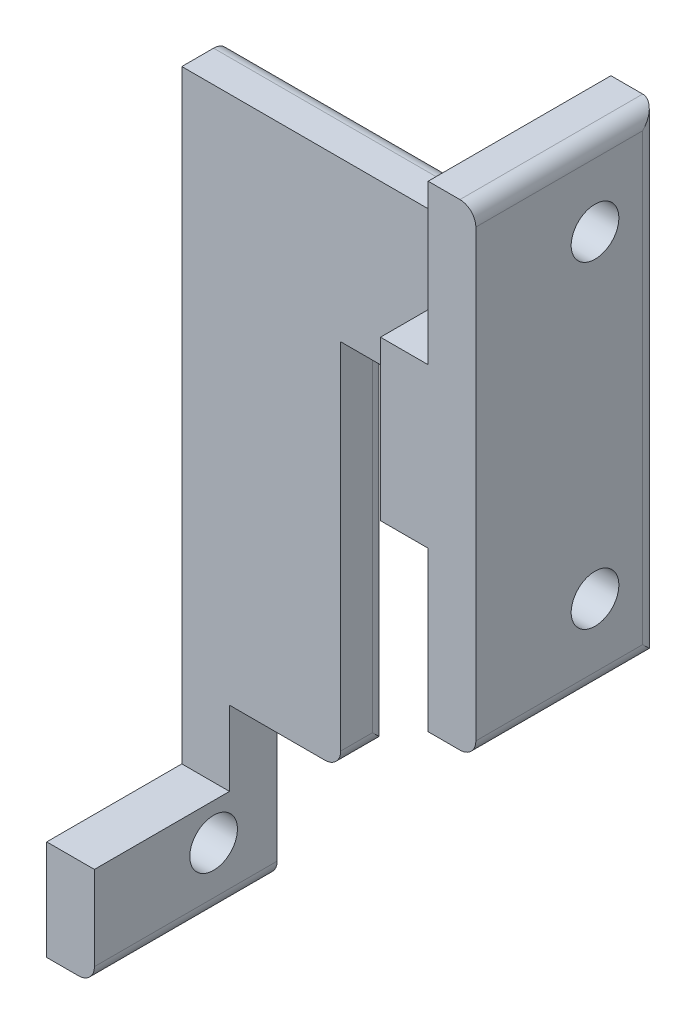
SolidWorks part; units mm, degrees
ref_plane "Alzado" through (0, 0, 0) normal (0, 0, 1) x (1, 0, 0)
ref_plane "Planta" through (0, 0, 0) normal (0, 1, 0) x (1, 0, 0)
ref_plane "Vista lateral" through (0, 0, 0) normal (1, 0, 0) x (0, 0, -1)
sketch "Croquis1" plane through (0, 0, 0) normal (1, 0, 0) x (0, 0, -1)
  line L1 (-23, 0) -> (0, 0)
  line L2 (-23, 0) -> (-23, -33.3)
  line L3 (-23, -33.3) -> (0, -33.3)
  line L4 (0, 0) -> (0, -33.3)
  dimension "D1" = 33.3
  dimension "D2" = 23
extrude "Saliente-Extruir2" add sketch "Croquis1" along normal blind 7
sketch "Croquis3" plane through (0, 0, 0) normal (0, 1, 0) x (1, 0, 0)
  line L0 (7, 0) -> (7, -23) construction
  line L1 (7, -3) -> (3, -3)
  line L2 (7, -3) -> (7, -22)
  line L3 (7, -22) -> (3, -22)
  line L4 (3, -3) -> (3, -22)
  line L5 (7, 0) -> (0, 0) construction
  line L6 (7, -23) -> (0, -23) construction
  line L7 (0, 0) -> (0, -23) construction
  dimension "D1" = 3
  dimension "D2" = 1
  dimension "D3" = 3
extrude "Cortar-Extruir1" cut sketch "Croquis3" against normal through all
sketch "Croquis7" plane through (0, 0, 0) normal (-1, 0, 0) x (0, 0, 1)
  line L0 (23, -33.3) -> (0, -33.3) construction
  line L1 (-7, 15) -> (30, 15)
  line L2 (-7, 15) -> (-7, -44.3)
  line L3 (-7, -44.3) -> (30, -44.3)
  line L4 (30, 15) -> (30, -44.3)
  line L5 (0, 0) -> (23, 0) construction
  line L6 (23, 0) -> (23, -33.3) construction
  line L7 (0, -33.3) -> (0, 0) construction
  line L9 (-7, 15) -> (0, 15)
  line L10 (-7, 15) -> (-7, 0)
  line L11 (-7, 0) -> (0, 0)
  line L12 (0, 15) -> (0, 0)
  line L13 (23, 0) -> (30, 0)
  line L14 (23, 0) -> (23, 15)
  line L15 (23, 15) -> (30, 15)
  line L16 (30, 0) -> (30, 15)
  line L17 (23, -33.3) -> (30, -33.3)
  line L18 (23, -33.3) -> (23, -44.3)
  line L19 (23, -44.3) -> (30, -44.3)
  line L20 (30, -33.3) -> (30, -44.3)
  line L21 (0, -33.3) -> (-7, -33.3)
  line L22 (0, -33.3) -> (0, -44.3)
  line L23 (0, -44.3) -> (-7, -44.3)
  line L24 (-7, -33.3) -> (-7, -44.3)
  circle A0 centre (-4, -15) radius 1.5
  circle A1 centre (-4, -28.3) radius 1.5
  circle A2 centre (27, -28.3) radius 1.5
  circle A3 centre (27, -15) radius 1.5
  circle A4 centre (4, 11) radius 1.5
  circle A5 centre (19, 11) radius 1.5
  circle A6 centre (4, -40.3) radius 1.5
  circle A7 centre (19, -40.3) radius 1.5
  dimension "D6" = 15
  dimension "D7" = 3
  dimension "D9" = 3
  dimension "D10" = 5
  dimension "D12" = 4
  dimension "D13" = 4
  dimension "D14" = 3
  dimension "D15" = 4
  dimension "D16" = 4
  dimension "D17" = 3
  dimension "D18" = 5
  dimension "D19" = 3
  dimension "D20" = 3
  dimension "D21" = 3
  dimension "D22" = 15
  dimension "D23" = 3
  dimension "D24" = 3
  dimension "D25" = 4
  dimension "D26" = 4
  dimension "D27" = 4
  dimension "D28" = 4
  dimension "D5" = 3
  dimension "D8" = 3
  dimension "D11" = 3
  dimension "D1" = 11
  dimension "D2" = 15
  dimension "D3" = 7
  dimension "D4" = 7
extrude "Saliente-Extruir3" add sketch "Croquis7" along normal blind 3 separate body
sketch "Croquis8" plane through (0, 0, 23) normal (0, 0, 1) x (1, 0, 0)
  line L1 (0, 0) -> (18, 0)
  line L2 (0, 0) -> (0, -10)
  line L3 (0, -10) -> (18, -10)
  line L4 (18, 0) -> (18, -10)
  circle A1 centre (15, -5) radius 1.5
  circle A2 centre (3, -5) radius 1.5
  dimension "D3" = 12
  dimension "D2" = 3
  dimension "D5" = 3
  dimension "D6" = 5
  dimension "D4" = 3
  dimension "D7" = 5
  dimension "D1" = 10
  dimension "D8" = 3
extrude "Saliente-Extruir5" add sketch "Croquis8" against normal blind 1
sketch "Croquis9" plane through (0, 0, 0) normal (0, 0, -1) x (-1, 0, 0)
  line L1 (0, 0) -> (-18, 0)
  line L2 (0, 0) -> (0, -10)
  line L3 (0, -10) -> (-18, -10)
  line L4 (-18, 0) -> (-18, -10)
  circle A1 centre (-15, -5) radius 1.5
  dimension "D1" = 3
extrude "Saliente-Extruir6" add sketch "Croquis9" against normal blind 3
sketch "Croquis10" plane through (18, 0, 0) normal (1, 0, 0) x (0, 0, -1)
  line L1 (-23, 0) -> (0, 0)
  line L2 (-23, 0) -> (-23, -10)
  line L3 (-23, -10) -> (0, -10)
  line L4 (0, 0) -> (0, -10)
extrude "Saliente-Extruir7" add sketch "Croquis10" along normal blind 3
sketch "Croquis11" plane through (3, 0, 0) normal (1, 0, 0) x (0, 0, -1)
  line L0 (-22, -33.3) -> (-22, 0) construction
  line L1 (-22, 0) -> (-3, 0)
  line L2 (-22, 0) -> (-22, -38)
  line L3 (-22, -38) -> (-3, -38)
  line L4 (-3, 0) -> (-3, -38)
  dimension "D1" = 38
  dimension "D2" = 19
extrude "Cortar-Extruir5" cut sketch "Croquis11" against normal through all
sketch "Croquis14" plane through (0, 0, 23) normal (0, 0, 1) x (1, 0, 0)
  line L0 (0, -38.8) -> (0, -33.3) construction
  line L1 (0, -33.3) -> (0, -44.3) construction
  line L2 (0, 0) -> (0, -33.3) construction
  line L3 (7, -10) -> (7, -33.3) construction
  line L4 (7, -17.3) -> (0, -17.3)
  line L5 (7, -17.3) -> (7, -33.3)
  line L6 (7, -33.3) -> (0, -33.3)
  line L7 (0, -17.3) -> (0, -33.3)
  line L8 (0, -33.3) -> (7, -33.3) construction
  line L9 (7, -33.3) -> (0, -33.3) construction
  dimension "D1" = 16
  dimension "D2" = 16
  dimension "D3" = 0
extrude "Cortar-Extruir7" cut sketch "Croquis14" against normal blind 1
sketch "Croquis15" plane through (0, 0, 0) normal (1, 0, 0) x (0, 0, -1)
  line L0 (-30, 0) -> (-30, -33.3) construction
  line L1 (-30, 0) -> (-23, 0)
  line L2 (-30, 0) -> (-30, -10)
  line L3 (-30, -10) -> (-23, -10)
  line L4 (-23, 0) -> (-23, -10)
  line L5 (7, 0) -> (0, 0)
  line L6 (7, 0) -> (7, -10)
  line L7 (7, -10) -> (0, -10)
  line L8 (0, 0) -> (0, -10)
extrude "Cortar-Extruir8" cut sketch "Croquis15" against normal through all
sketch "Croquis17" plane through (21, 0, 0) normal (1, 0, 0) x (0, 0, -1)
  line L0 (0, -33.3) -> (0, -10) construction
  line L1 (-23, -10) -> (0, -10)
  line L2 (-23, -10) -> (-23, -20)
  line L3 (-23, -20) -> (0, -20)
  line L4 (0, -10) -> (0, -20)
  line L6 (-23, -10) -> (0, -10)
  line L7 (-23, -10) -> (-23, 10)
  line L8 (-23, 10) -> (0, 10)
  line L9 (0, -10) -> (0, 10)
  circle A0 centre (-19, 5) radius 1.5
  circle A1 centre (-4, 5) radius 1.5
  circle A2 centre (-19, -15) radius 1.5
  circle A3 centre (-4, -15) radius 1.5
  line M7 (-23, 0) -> (-23, -10)
  line M8 (-23, -10) -> (0, -10)
  line M9 (0, -10) -> (0, 0)
  line M10 (0, 0) -> (-23, 0)
  dimension "D3" = 3
  dimension "D4" = 3
  dimension "D5" = 5
  dimension "D6" = 4
  dimension "D7" = 5
  dimension "D8" = 4
  dimension "D9" = 3
  dimension "D10" = 3
  dimension "D11" = 4
  dimension "D12" = 4
  dimension "D13" = 5
  dimension "D14" = 5
  dimension "D1" = 20
  dimension "D2" = 10
extrude "Saliente-Extruir8" add sketch "Croquis17" along normal blind 3 contours L4 L2 L3 A3 A2 M8 | M10 M7 M8 M9 | L9 L8 L7 A1 A0 M10
fillet "Redondeo2" radius 1 16 edges at (0, -38.8, 23) (0, -44.3, 11.5) (0, -10, 26.5) (0, -33.3, 26.5) (0, -21.65, 30) (7, -33.3, 1.5) (0, -33.3, -3.5) (0, -10, -3.5) (0, -21.65, -7) (7, -21.65, 0) (24, 10, 11.5) (24, -5, 0) (24, -20, 11.5) (24, -5, 23)
sketch "Croquis18" plane through (0, -44.3, 0) normal (0, -1, 0) x (-1, 0, 0)
  line L0 (3, -11.5) -> (-24, -11.5) construction
  line L1 (3, 0) -> (3, -23) construction
  line L3 (3, -30) -> (1, -30) construction
  line L4 (3, -11.5) -> (-24, -11.5)
  line L5 (3, -11.5) -> (3, -30)
  line L6 (3, -30) -> (-24, -30)
  line L8 (-24, -11.5) -> (-24, -30)
  line L9 (-24, -22) -> (-24, -1) construction
  dimension "D1" = 0
  dimension "D2" = 0
extrude "Cortar-Extruir10" cut sketch "Croquis18" against normal through all
